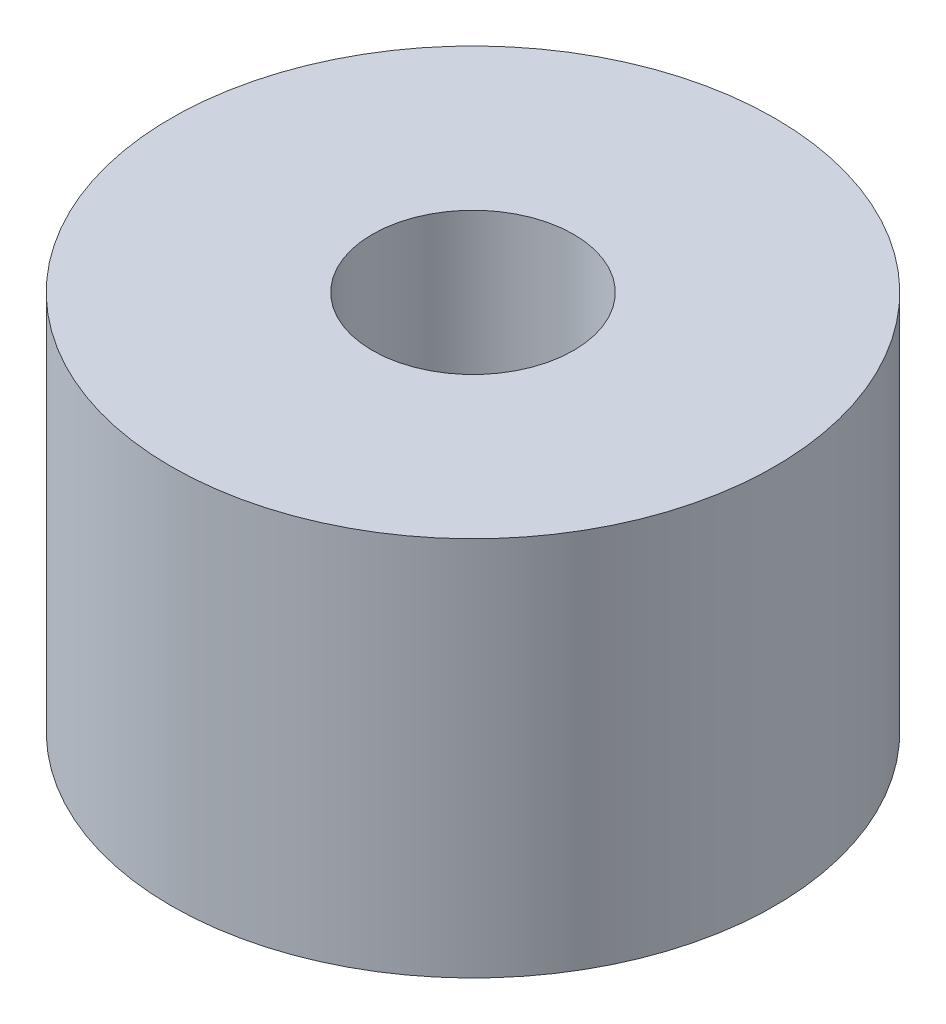
SolidWorks part; units mm, degrees
ref_plane "Alzado" through (0, 0, 0) normal (0, 0, 1) x (1, 0, 0)
ref_plane "Planta" through (0, 0, 0) normal (0, 1, 0) x (1, 0, 0)
ref_plane "Vista lateral" through (0, 0, 0) normal (1, 0, 0) x (0, 0, -1)
sketch "Croquis1" plane through (0, 0, 0) normal (0, 1, 0) x (1, 0, 0)
  circle A0 centre (0, 0) radius 4.76
  circle A1 centre (0, 0) radius 1.5875
  dimension "D1" = 3.175
  dimension "D2" = 9.52
extrude "Saliente-Extruir1" add sketch "Croquis1" along normal blind 6
